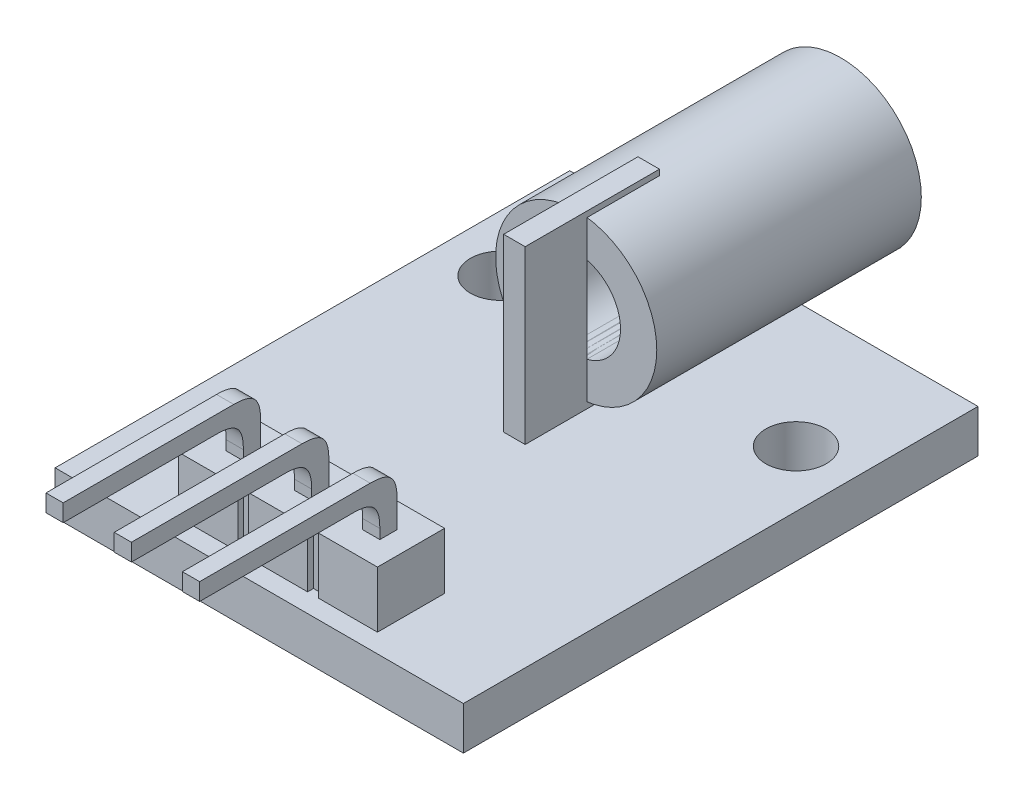
SolidWorks part; units mm, degrees
ref_plane "Front Plane" through (0, 0, 0) normal (0, 0, 1) x (1, 0, 0)
ref_plane "Top Plane" through (0, 0, 0) normal (0, 1, 0) x (1, 0, 0)
ref_plane "Right Plane" through (0, 0, 0) normal (1, 0, 0) x (0, 0, -1)
sketch "Sketch1" plane through (0, 0, 0) normal (0, 1, 0) x (1, 0, 0)
  line L1 (-7.6, -9.58) -> (7.6, -9.58)
  line L2 (-7.6, -9.58) -> (-7.6, 9.58)
  line L3 (-7.6, 9.58) -> (7.6, 9.58)
  line L4 (7.6, -9.58) -> (7.6, 9.58)
  line L5 (-7.6, -9.58) -> (7.6, 9.58) construction
  line L6 (-7.6, 9.58) -> (7.6, -9.58) construction
  point P0 (0, 0)
  dimension "D1" = 15.2
  dimension "D2" = 19.16
extrude "Boss-Extrude1" add sketch "Sketch1" against normal blind 1.6
sketch "Sketch2" plane through (0, 0, 0) normal (0, 1, 0) x (1, 0, 0)
  line L0 (-5.5, 4.905) -> (5.5, 4.905) construction
  line L1 (0, 4.905) -> (0, 9.58) construction
  line L2 (7.6, 9.58) -> (-7.6, 9.58) construction
  circle A0 centre (-5.5, 4.905) radius 1.125
  circle A1 centre (5.5, 4.905) radius 1.125
  dimension "D1" = 3.55
  dimension "D2" = 2.25
  dimension "D3" = 8.75
extrude "Cut-Extrude1" cut sketch "Sketch2" against normal through all
sketch "Sketch3" plane through (0, 0, 0) normal (0, 1, 0) x (1, 0, 0)
  line L0 (-3.7, -7.63) -> (3.7, -7.63) construction
  line L1 (-3.7, -6.38) -> (-1.5, -6.38)
  line L2 (-3.7, -6.38) -> (-3.7, -8.88)
  line L3 (-3.7, -8.88) -> (-1.5, -8.88)
  line L4 (-1.5, -6.38) -> (-1.5, -6.5986)
  line L5 (-1.1, -6.38) -> (1.1, -6.38)
  line L6 (-1.1, -6.38) -> (-1.1, -6.5986)
  line L7 (-1.1, -8.88) -> (1.1, -8.88)
  line L8 (1.1, -6.38) -> (1.1, -6.5986)
  line L9 (1.5, -6.38) -> (3.7, -6.38)
  line L10 (1.5, -6.38) -> (1.5, -6.5986)
  line L11 (1.5, -8.88) -> (3.7, -8.88)
  line L12 (3.7, -6.38) -> (3.7, -8.88)
  line L13 (-1.5, -6.5986) -> (-1.1, -6.5986)
  line L15 (-1.5, -8.6614) -> (-1.1, -8.6614)
  line L17 (1.1, -6.5986) -> (1.5, -6.5986)
  line L19 (1.1, -8.6614) -> (1.5, -8.6614)
  line L21 (-7.6, -9.58) -> (7.6, -9.58) construction
  line L22 (-1.5, -8.6614) -> (-1.5, -8.88)
  line L23 (-1.1, -8.6614) -> (-1.1, -8.88)
  line L24 (1.1, -8.6614) -> (1.1, -8.88)
  line L25 (1.5, -8.6614) -> (1.5, -8.88)
  point P20 (0, -7.63)
  point P24 (0, -9.58)
  dimension "D1" = 7.4
  dimension "D2" = 2.2
  dimension "D3" = 2.5
  dimension "D4" = 0.7
  dimension "D5" = 0.2186
extrude "Boss-Extrude2" add sketch "Sketch3" along normal blind 2.1
ref_plane "Plane1" through (0, 0, 0) normal (1, 0, 0) x (0, 0, -1)
sketch "Sketch4" plane through (0, 0, 0) normal (1, 0, 0) x (0, 0, -1)
  line L0 (-8.88, 2.1) -> (-6.38, 2.1) construction
  line L1 (-7.95, 2.1) -> (-7.31, 2.1)
  line L2 (-7.95, 2.1) -> (-7.95, 3.46)
  line L4 (-7.31, 2.1) -> (-7.31, 4.1)
  line L6 (-7.31, 4.1) -> (-14.66, 4.1)
  line L8 (-7.95, 3.46) -> (-14.66, 3.46)
  line L9 (-14.66, 4.1) -> (-14.66, 3.46)
  point P2 (-7.63, 2.1)
  point P11 (-7.63, 2.1)
  dimension "D1" = 2
  dimension "D2" = 7.35
  dimension "D3" = 0.64
  dimension "D4" = 0.64
extrude "Boss-Extrude3" add sketch "Sketch4" along normal blind 0.32 and the other way blind 0.32
fillet "Fillet1" radius 1 2 edges at (0, 3.46, 7.95) (0, 4.1, 7.31) conic rho 0.55
pattern_linear "LPattern1" count 2 spacing 2.54 along (-1, 0, 0) count 2 spacing 2.54 along (1, 0, 0) of "Boss-Extrude3", "Fillet1" pattern seed only yes
sketch "Sketch5" plane through (0, 0, 0) normal (0, 1, 0) x (1, 0, 0)
  line L0 (-7.6, -9.58) -> (7.6, -9.58) construction
  line L1 (-0.4, 4.92) -> (0.4, 4.92)
  line L2 (-0.4, 4.92) -> (-0.4, -0.08)
  line L3 (-0.4, -0.08) -> (0.4, -0.08)
  line L4 (0.4, 4.92) -> (0.4, -0.08)
  line L5 (-0.4, 4.92) -> (0.4, -0.08) construction
  line L6 (-0.4, -0.08) -> (0.4, 4.92) construction
  point P0 (0, 2.42)
  dimension "D1" = 9.5
  dimension "D2" = 5
  dimension "D3" = 0.8
extrude "Boss-Extrude4" add sketch "Sketch5" along normal blind 6.38
ref_plane "Plane2" through (0, 0, -2.22) normal (0, 0, 1) x (1, 0, 0)
sketch "Sketch6" plane through (0, 0, -2.22) normal (0, 0, 1) x (1, 0, 0)
  line L6 (0, -1.155) -> (0, 1.155) construction
  line L9 (-7.6, 0) -> (7.6, 0) construction
  circle A2 centre (0, 3.2) radius 3
  dimension "D1" = 6
  dimension "D2" = 0.2
extrude "Boss-Extrude7" add sketch "Sketch6" against normal blind 9.85 separate body
sketch "Sketch8" plane through (0, 0, -12.07) normal (0, 0, -1) x (-1, 0, 0)
  line L0 (0, 1.155) -> (0, -1.155) construction
  circle A0 centre (0, 3.2) radius 1.65
  circle A1 centre (0, 3.2) radius 3 construction
  dimension "D1" = 3.3
extrude "Cut-Extrude2" cut sketch "Sketch8" against normal up to surface (9.85 mm away) up to face at (3, 3.2, -2.22)
sketch "Sketch9" plane through (0, -1.6, 0) normal (0, -1, 0) x (1, 0, 0)
  line L0 (2.22, 7.95) -> (2.22, 7.31) construction
  line L1 (2.22, 7.95) -> (2.86, 7.95) construction
  line L2 (-0.32, 7.95) -> (0.32, 7.95) construction
  line L3 (-0.32, 7.95) -> (-0.32, 7.31) construction
  line L4 (-0.32, 7.31) -> (0.32, 7.31) construction
  line L5 (0.32, 7.95) -> (0.32, 7.31) construction
  line L6 (2.22, 7.31) -> (2.86, 7.31) construction
  line L7 (2.86, 7.95) -> (2.86, 7.31) construction
  line L8 (-2.86, 7.31) -> (-2.22, 7.31) construction
  line L9 (-2.22, 7.95) -> (-2.22, 7.31) construction
  line L10 (-2.86, 7.95) -> (-2.86, 7.31) construction
  line L11 (-2.86, 7.95) -> (-2.22, 7.95) construction
  line L12 (2.22, 7.95) -> (2.22, 7.31)
  line L13 (2.22, 7.95) -> (2.86, 7.95)
  line L14 (-0.32, 7.95) -> (0.32, 7.95)
  line L15 (-0.32, 7.95) -> (-0.32, 7.31)
  line L16 (-0.32, 7.31) -> (0.32, 7.31)
  line L17 (0.32, 7.95) -> (0.32, 7.31)
  line L18 (2.22, 7.31) -> (2.86, 7.31)
  line L19 (2.86, 7.95) -> (2.86, 7.31)
  line L20 (-2.86, 7.31) -> (-2.22, 7.31)
  line L21 (-2.22, 7.95) -> (-2.22, 7.31)
  line L22 (-2.86, 7.95) -> (-2.86, 7.31)
  line L23 (-2.86, 7.95) -> (-2.22, 7.95)
extrude "Boss-Extrude11" add sketch "Sketch9" along normal blind 1.38
ref_axis "Axis1" through (0, 3.2, -1.3228) along (0, 0, -1)
sketch "Sketch10" plane through (0, -1.6, 0) normal (0, -1, 0) x (1, 0, 0)
  line L0 (0, 9.58) -> (0, -9.58) construction
  line L1 (-7.6, 9.58) -> (7.6, 9.58) construction
  line L2 (7.6, -9.58) -> (-7.6, -9.58) construction
  line L3 (-7.6, 0) -> (7.6, 0) construction
  line L4 (-7.6, -9.58) -> (-7.6, 9.58) construction
  line L5 (7.6, 9.58) -> (7.6, -9.58) construction
